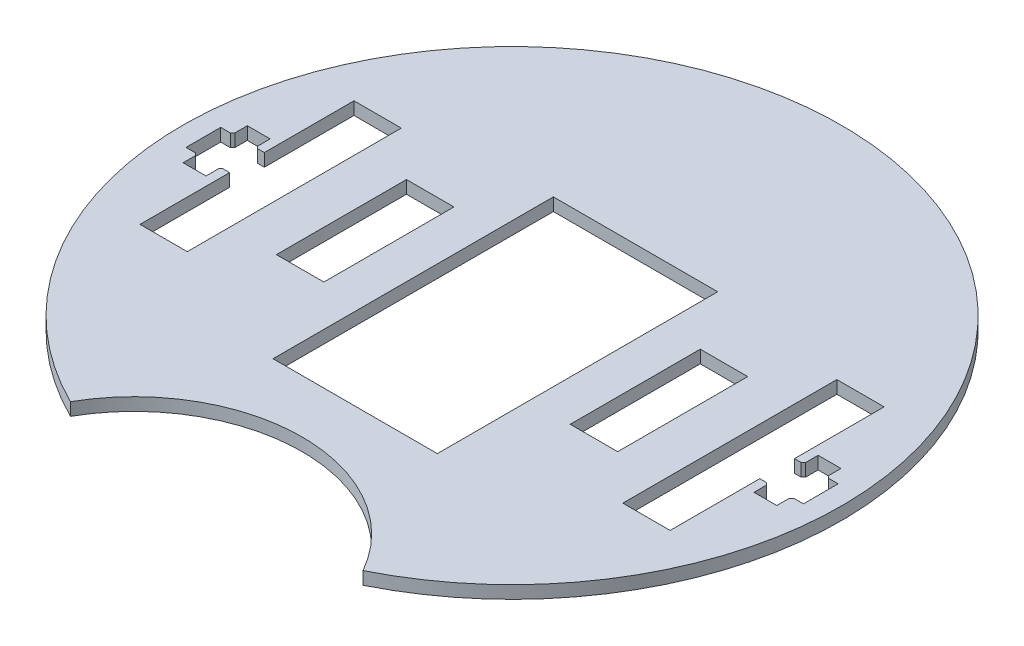
SolidWorks part; units mm, degrees
ref_plane "Front Plane" through (0, 0, 0) normal (0, 0, 1) x (1, 0, 0)
ref_plane "Top Plane" through (0, 0, 0) normal (0, 1, 0) x (1, 0, 0)
ref_plane "Right Plane" through (0, 0, 0) normal (1, 0, 0) x (0, 0, -1)
sketch "Sketch1" plane through (0, 0, 0) normal (0, 1, 0) x (1, 0, 0)
  line L0 (0, -86.0416) -> (-33.2911, -67.2064) construction
  line L1 (0, -86.0416) -> (0, 0) construction
  arc A0 (33.2911, -67.2064) -> (-33.2911, -67.2064) centre (0, 0) ccw
  arc A1 (33.2911, -67.2064) -> (-33.2911, -67.2064) centre (0, -86.0416) ccw
  dimension "D1" = 150
  dimension "D2" = 76.5
  dimension "D3" = 60.5
extrude "Boss-Extrude1" add sketch "Sketch1" along normal blind 2.9
sketch "solenoid placement" plane through (0, 2.9, 0) normal (0, 1, 0) x (1, 0, 0)
  line L4 (-18.7, -35.7) -> (18.7, -35.7)
  line L5 (18.7, -35.7) -> (18.7, 28.1)
  line L6 (18.7, 28.1) -> (-18.7, 28.1)
  line L7 (-18.7, 28.1) -> (-18.7, -35.7)
  line L8 (-18.7, -35.7) -> (18.7, -35.7)
  line L9 (18.7, -35.7) -> (18.7, 28.1)
  line L10 (18.7, 28.1) -> (-18.7, 28.1)
  line L11 (-18.7, 28.1) -> (-18.7, -35.7)
  circle A1 centre (0, 0) radius 75 construction
  arc A2 (33.2911, -67.2064) -> (-33.2911, -67.2064) centre (0, 0) ccw construction
  dimension "D1" = 0
extrude "Cut-Extrude1" cut sketch "solenoid placement" against normal through all
sketch "Sketch2" plane through (0, 2.9, 0) normal (0, 1, 0) x (1, 0, 0)
  line L0 (49.8627, -24.0528) -> (49.8627, 24.0528) construction
  line L1 (-60.0227, -24.0528) -> (-49.8627, -24.0528) construction
  line L2 (-60.0227, -24.0528) -> (-60.0227, 24.0528) construction
  line L3 (-60.0227, 24.0528) -> (-49.8627, 24.0528) construction
  line L4 (-49.8627, -24.0528) -> (-49.8627, 24.0528) construction
  line L5 (60.0227, 24.0528) -> (49.8627, 24.0528) construction
  line L6 (60.0227, -24.0528) -> (60.0227, 24.0528) construction
  line L7 (60.0227, -24.0528) -> (49.8627, -24.0528) construction
  line L8 (60.3227, -24.3528) -> (60.3227, 24.3528)
  line L9 (60.3227, -24.3528) -> (49.5627, -24.3528)
  line L10 (49.5627, -24.3528) -> (49.5627, 24.3528)
  line L11 (60.3227, 24.3528) -> (49.5627, 24.3528)
  line L12 (0, 0) -> (0, 75) construction
  line L13 (-60.3227, 24.3528) -> (-49.5627, 24.3528)
  line L14 (-49.5627, -24.3528) -> (-49.5627, 24.3528)
  line L15 (-60.3227, -24.3528) -> (-49.5627, -24.3528)
  line L16 (-60.3227, -24.3528) -> (-60.3227, 24.3528)
  arc A0 (33.2911, -67.2064) -> (-33.2911, -67.2064) centre (0, 0) ccw construction
extrude "Cut-Extrude2" cut sketch "Sketch2" against normal through all
sketch "Sketch3" plane through (0, 2.9, 0) normal (0, 1, 0) x (1, 0, 0)
  line L4 (-38.8327, -14.8) -> (-28.0327, -14.8)
  line L5 (-28.0327, -14.8) -> (-28.0327, 14.8)
  line L6 (-28.0327, 14.8) -> (-38.8327, 14.8)
  line L7 (-38.8327, 14.8) -> (-38.8327, -14.8)
  line L8 (-38.8327, -14.8) -> (-28.0327, -14.8)
  line L9 (-28.0327, -14.8) -> (-28.0327, 14.8)
  line L10 (-28.0327, 14.8) -> (-38.8327, 14.8)
  line L11 (-38.8327, 14.8) -> (-38.8327, -14.8)
  line L12 (38.8327, -14.8) -> (38.8327, 14.8)
  line L13 (38.8327, 14.8) -> (28.0327, 14.8)
  line L14 (28.0327, 14.8) -> (28.0327, -14.8)
  line L15 (28.0327, -14.8) -> (38.8327, -14.8)
  line L16 (38.8327, -14.8) -> (38.8327, 14.8)
  line L17 (38.8327, 14.8) -> (28.0327, 14.8)
  line L18 (28.0327, 14.8) -> (28.0327, -14.8)
  line L19 (28.0327, -14.8) -> (38.8327, -14.8)
  point P8 (0, 0)
  point P9 (0, 0)
  point P10 (0, 0)
  point P11 (0, 0)
  point P12 (0, 0)
  point P13 (0, 0)
  point P14 (0, 0)
  point P15 (0, 0)
  dimension "D1" = 0
  dimension "D2" = 0
extrude "Cut-Extrude3" cut sketch "Sketch3" against normal through all
sketch "Sketch4" plane through (0, 2.9, 0) normal (0, 1, 0) x (1, 0, 0)
  line L12 (-62.3527, 3.95) -> (-62.3527, 7.3)
  line L13 (-59.6527, 3.95) -> (-62.3527, 3.95)
  line L14 (-59.6527, -3.95) -> (-59.6527, 3.95)
  line L15 (-62.3527, -3.95) -> (-59.6527, -3.95)
  line L16 (-62.3527, -7.3) -> (-62.3527, -3.95)
  line L17 (-67.5527, -7.3) -> (-62.3527, -7.3)
  line L18 (-67.5527, -3.95) -> (-67.5527, -7.3)
  line L19 (-70.2527, -3.95) -> (-67.5527, -3.95)
  line L20 (-70.2527, 3.95) -> (-70.2527, -3.95)
  line L21 (-67.5527, 3.95) -> (-70.2527, 3.95)
  line L22 (-67.5527, 7.3) -> (-67.5527, 3.95)
  line L23 (-62.3527, 7.3) -> (-67.5527, 7.3)
  line L24 (-62.3527, 3.95) -> (-62.3527, 7.3)
  line L25 (-59.6527, 3.95) -> (-62.3527, 3.95)
  line L26 (-59.6527, -3.95) -> (-59.6527, 3.95)
  line L27 (-62.3527, -3.95) -> (-59.6527, -3.95)
  line L28 (-62.3527, -7.3) -> (-62.3527, -3.95)
  line L29 (-67.5527, -7.3) -> (-62.3527, -7.3)
  line L30 (-67.5527, -3.95) -> (-67.5527, -7.3)
  line L31 (-70.2527, -3.95) -> (-67.5527, -3.95)
  line L32 (-70.2527, 3.95) -> (-70.2527, -3.95)
  line L33 (-67.5527, 3.95) -> (-70.2527, 3.95)
  line L34 (-67.5527, 7.3) -> (-67.5527, 3.95)
  line L35 (-62.3527, 7.3) -> (-67.5527, 7.3)
  line L36 (67.5527, 3.95) -> (67.5527, 7.3)
  line L37 (70.2527, 3.95) -> (67.5527, 3.95)
  line L38 (70.2527, -3.95) -> (70.2527, 3.95)
  line L39 (67.5527, -3.95) -> (70.2527, -3.95)
  line L40 (67.5527, -7.3) -> (67.5527, -3.95)
  line L41 (62.3527, -7.3) -> (67.5527, -7.3)
  line L42 (62.3527, -3.95) -> (62.3527, -7.3)
  line L43 (59.6527, -3.95) -> (62.3527, -3.95)
  line L44 (59.6527, 3.95) -> (59.6527, -3.95)
  line L45 (62.3527, 3.95) -> (59.6527, 3.95)
  line L46 (62.3527, 7.3) -> (62.3527, 3.95)
  line L47 (67.5527, 7.3) -> (62.3527, 7.3)
  line L48 (67.5527, 3.95) -> (67.5527, 7.3)
  line L49 (70.2527, 3.95) -> (67.5527, 3.95)
  line L50 (70.2527, -3.95) -> (70.2527, 3.95)
  line L51 (67.5527, -3.95) -> (70.2527, -3.95)
  line L52 (67.5527, -7.3) -> (67.5527, -3.95)
  line L53 (62.3527, -7.3) -> (67.5527, -7.3)
  line L54 (62.3527, -3.95) -> (62.3527, -7.3)
  line L55 (59.6527, -3.95) -> (62.3527, -3.95)
  line L56 (59.6527, 3.95) -> (59.6527, -3.95)
  line L57 (62.3527, 3.95) -> (59.6527, 3.95)
  line L58 (62.3527, 7.3) -> (62.3527, 3.95)
  line L59 (67.5527, 7.3) -> (62.3527, 7.3)
  dimension "D1" = 0
  dimension "D2" = 0
extrude "Cut-Extrude4" cut sketch "Sketch4" against normal through all
chamfer "Chamfer1" distance 0.5 angle 45 8 edges at (67.5527, 1.45, 3.95) (67.5527, 1.45, -3.95) (62.3527, 1.45, 3.95) (62.3527, 1.45, -3.95) (-67.5527, 1.45, 3.95) (-62.3527, 1.45, 3.95) (-62.3527, 1.45, -3.95) (-67.5527, 1.45, -3.95)
equation "\"smallPulleyTeeth\"= 15"
equation "\"largePulleyTeeth\"= 30"
equation "\"eighthThick\"= 2.9mm"
equation "\"sixteenthThick\" = 1.7mm"
equation "\"wheelEighthThick\"=3.0mm"
equation "\"quarterThick\"=5.6mm"
equation "\"OD\" = 150mm"
equation "\"puckAngle\" = 60.5deg"
equation "\"D1@Sketch1\"=\"OD\""
equation "\"puckDiam\" = 76.5mm"
equation "\"D2@Sketch1\"=\"puckDiam\""
equation "\"D3@Sketch1\"=\"puckAngle\""
equation "\"D1@Boss-Extrude1\"=\"eighthThick\""
equation "\"axlePress\" = 5.8mm"
equation "\"press\" = 0.2mm"
equation "\"wheelClear\" = 0.3mm"
equation "\"D1@Sketch2\"=\"wheelClear\""
